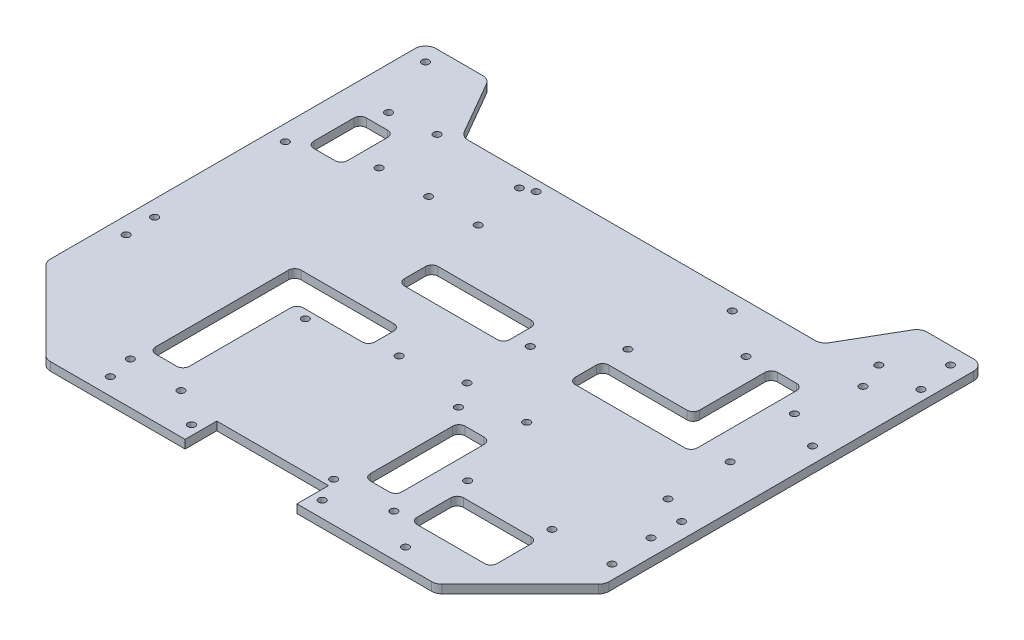
SolidWorks part; units mm, degrees
material "Acier non allié"
ref_plane "Front" through (0, 0, 0) normal (0, 0, 1) x (1, 0, 0)
ref_plane "Top" through (0, 0, 0) normal (0, 1, 0) x (1, 0, 0)
ref_plane "Right" through (0, 0, 0) normal (1, 0, 0) x (0, 0, -1)
sketch "Main scetch" plane through (0, 0, 0) normal (0, 1, 0) x (1, 0, 0)
  line L1 (0, 0) -> (132.5, 0) construction
  line L2 (0, 0) -> (0, 220) construction
  line L3 (0, 220) -> (132.5, 220) construction
  line L4 (132.5, 0) -> (132.5, 220) construction
  line L13 (-92.5, 0) -> (92.5, 0)
  line L14 (92.5, 0) -> (132.5, 40)
  line L15 (132.5, 40) -> (132.5, 220)
  line L16 (132.5, 220) -> (102.5, 220)
  line L17 (102.5, 220) -> (85.1795, 190)
  line L18 (85.1795, 190) -> (-85.1795, 190)
  line L19 (-102.5, 220) -> (-85.1795, 190)
  line L20 (-132.5, 220) -> (-102.5, 220)
  line L21 (-132.5, 40) -> (-132.5, 220)
  line L22 (-92.5, 0) -> (-132.5, 40)
  point P11 (0, 190)
  dimension "132.5" = 132.5
  dimension "D2" = 220
  dimension "D1" = 40
  dimension "D3" = 40
  dimension "D4" = 30
  dimension "D5" = 60
  dimension "D6" = 30
extrude "Main extrusion" add sketch "Main scetch" along normal blind 4
fillet "Congé1" radius 5 10 edges at (-132.5, 2, -40) (-92.5, 2, 0) (92.5, 2, 0) (132.5, 2, -40) (132.5, 2, -220) (102.5, 2, -220) (85.1795, 2, -190) (-85.1795, 2, -190) (-102.5, 2, -220) (-132.5, 2, -220)
sketch "Esquisse1" plane through (0, 4, 0) normal (0, 1, 0) x (1, 0, 0)
  line L0 (0, 0) -> (0, 218.5516) construction
  line L1 (132.5, 42.0711) -> (132.5, 215) construction
  line L2 (127.5, 220) -> (105.3868, 220) construction
  line L3 (-90.4289, 0) -> (90.4289, 0) construction
  circle A0 centre (70, 8) radius 1
  circle A1 centre (124.5, 70) radius 1
  circle A2 centre (124.5, 212) radius 1
  circle A3 centre (-124.5, 212) radius 1
  circle A4 centre (-124.5, 70) radius 1
  circle A5 centre (-70, 8) radius 1
  dimension "D1" = 2
  dimension "D2" = 2
  dimension "D3" = 2
  dimension "D4" = 8
  dimension "D5" = 8
  dimension "D6" = 8
  dimension "D7" = 8
  dimension "D8" = 70
  dimension "D9" = 70
extrude "Enlèv. mat.-Extru.1" cut sketch "Esquisse1" against normal through all
hole_wizard "Dégagement M31" positions "Esquisse2" profile "Esquisse3" hole size "M3" standard "ISO" end condition through all
sketch "Esquisse2" plane through (0, 4, 0) normal (0, 1, 0) x (1, 0, 0)
  point P0 (-124.5, 212)
  point P3 (-124.5, 70)
  point P6 (-70, 8)
  point P9 (70, 8)
  point P12 (124.5, 70)
  point P15 (124.5, 212)
sketch "Esquisse3" plane through (-124.5, 4, -212) normal (1, 0, 0) x (0, 0, 1)
  line L0 (0, 0) -> (0, 4)
  line L1 (0, 4) -> (1.7, 4)
  line L2 (1.7, 4) -> (1.7, 0)
  line L5 (1.7, 0) -> (0, 0)
  line L11 (0, -6.35) -> (0, 107.95) construction
  dimension "Diamètre du perçage jusqu'au prochain" = 3.4
  dimension "Profondeur du perçage jusqu'au prochain" = 4
sketch "Esquisse4" plane through (0, 4, 0) normal (0, 1, 0) x (1, 0, 0)
  line L0 (-132.5, 215) -> (-132.5, 42.0711) construction
  line L1 (-125, 146) -> (-125, 84) construction
  line L2 (82.2927, 190) -> (-82.2927, 190) construction
  line L3 (132.5, 42.0711) -> (132.5, 215) construction
  line L4 (-90.4289, 0) -> (90.4289, 0) construction
  line L5 (127.5, 220) -> (105.3868, 220) construction
  line L8 (-105.3868, 220) -> (-127.5, 220) construction
  line L9 (-31, 7.5) -> (31, 7.5) construction
  line L10 (125, 146) -> (125, 84) construction
  line L11 (-26.5, 0) -> (26.5, 0)
  line L12 (-26.5, 0) -> (-26.5, 15)
  line L13 (-26.5, 15) -> (26.5, 15)
  line L14 (26.5, 0) -> (26.5, 15)
  line L15 (50.5, 182.5) -> (112.5, 182.5) construction
  line L16 (-112.5, 182.5) -> (-50.5, 182.5) construction
  circle A1 centre (-68.5, 185) radius 1 construction
  circle A5 centre (72.5, 167) radius 1
  circle A6 centre (41.5, 142) radius 1
  circle A7 centre (107.5, 155) radius 1
  circle A8 centre (127.5, 195) radius 1
  circle A9 centre (112, 120) radius 1
  circle A10 centre (112.5, 90) radius 1
  circle A11 centre (17.2, 120) radius 1
  circle A12 centre (17.2, 90) radius 1
  circle A13 centre (47.5, 88) radius 1
  circle A14 centre (57.5, 50) radius 1
  circle A15 centre (97.5, 50) radius 1
  circle A16 centre (52.5, 20) radius 1
  circle A17 centre (-10, 85) radius 1
  circle A18 centre (-72.5, 20) radius 1
  circle A19 centre (107.5, 195) radius 1
  circle A23 centre (-47.5, 78) radius 1
  circle A24 centre (25.14, 78) radius 1
  circle A25 centre (-47.5, 19.07) radius 1
  circle A26 centre (25.1096, 18.82) radius 1
  circle A31 centre (-125, 146) radius 1
  circle A32 centre (-125, 84) radius 1
  circle A33 centre (-31, 7.5) radius 1
  circle A34 centre (31, 7.5) radius 1
  circle A35 centre (125, 146) radius 1
  circle A36 centre (125, 84) radius 1
  circle A37 centre (50.5, 182.5) radius 1
  circle A38 centre (112.5, 182.5) radius 1
  circle A39 centre (-112.5, 182.5) radius 1
  circle A40 centre (-50.5, 182.5) radius 1
  circle A41 centre (-45, 185) radius 1
  circle A42 centre (-45, 157.5) radius 1
  circle A43 centre (-68.5, 157.5) radius 1
  circle A44 centre (-92, 157.5) radius 1
  circle A45 centre (-92, 185) radius 1
  circle A46 centre (126, 50) radius 1.5
  point P63 (-125, 115)
  point P69 (0, 7.5)
  point P74 (0, 15)
  point P79 (125, 115)
  dimension "D4" = 2
  dimension "D13" = 2
  dimension "D16" = 2
  dimension "D19" = 2
  dimension "D24" = 2
  dimension "D25" = 2
  dimension "D28" = 2
  dimension "D30" = 2
  dimension "D32" = 2
  dimension "D36" = 2
  dimension "D37" = 2
  dimension "D40" = 2
  dimension "D48" = 2
  dimension "D49" = 2
  dimension "D50" = 2
  dimension "D52" = 2
  dimension "D11" = 2
  dimension "D12" = 2
  dimension "D65" = 2
  dimension "D66" = 2
  dimension "D72" = 2
  dimension "D73" = 2
  dimension "D77" = 2
  dimension "D78" = 2
  dimension "D85" = 2
  dimension "D86" = 2
  dimension "D89" = 2
  dimension "D90" = 2
  dimension "D94" = 2
  dimension "D95" = 2
  dimension "D58" = 2
  dimension "D59" = 2
  dimension "D62" = 2
  dimension "D63" = 2
  dimension "D69" = 2
  dimension "D99" = 3
  dimension "D14" = 205
  dimension "D15" = 23
  dimension "D20" = 25
  dimension "D21" = 65
  dimension "D22" = 5
  dimension "D23" = 25
  dimension "D26" = 20.5
  dimension "D27" = 100
  dimension "D29" = 30
  dimension "D31" = 115.3
  dimension "D33" = 115.3
  dimension "D34" = 132
  dimension "D35" = 85
  dimension "D38" = 50
  dimension "D39" = 75
  dimension "D41" = 35
  dimension "D42" = 80
  dimension "D43" = 20
  dimension "D44" = 20
  dimension "D45" = 205
  dimension "D46" = 85
  dimension "D47" = 142.5
  dimension "D51" = 25
  dimension "D53" = 25
  dimension "D54" = 5
  dimension "D55" = 64
  dimension "D7" = 59.18
  dimension "D8" = 72.64
  dimension "D9" = 58.93
  dimension "D10" = 72.61
  dimension "D67" = 85
  dimension "D68" = 78
  dimension "D17" = 25
  dimension "D18" = 31
  dimension "D76" = 62
  dimension "D74" = 7.5
  dimension "D75" = 105
  dimension "D79" = 7.5
  dimension "D80" = 132.5
  dimension "D81" = 62
  dimension "D82" = 15
  dimension "D83" = 53
  dimension "D84" = 62
  dimension "D87" = 7.5
  dimension "D88" = 105
  dimension "D91" = 62
  dimension "D92" = 7.5
  dimension "D96" = 62
  dimension "D97" = 7.5
  dimension "D98" = 20
  dimension "D93" = 20
  dimension "D56" = 87.5
  dimension "D57" = 5
  dimension "D60" = 27.5
  dimension "D61" = 23.5
  dimension "D64" = 23.5
  dimension "D70" = 27.5
  dimension "D71" = 50
  dimension "D100" = 6.5
extrude "Enlèv. mat.-Extru.2" cut sketch "Esquisse4" against normal through all
hole_wizard "Dégagement M32" positions "Esquisse5" profile "Esquisse6" hole size "M3" standard "ISO" end condition through all
sketch "Esquisse5" plane through (0, 4, 0) normal (0, 1, 0) x (1, 0, 0)
  point P9 (17.2, 120)
  point P18 (41.5, 142)
  point P21 (72.5, 167)
  point P24 (107.5, 155)
  point P27 (127.5, 195)
  point P30 (112, 120)
  point P33 (112.5, 90)
  point P36 (47.5, 88)
  point P39 (17.2, 90)
  point P42 (57.5, 50)
  point P45 (97.5, 50)
  point P48 (-10, 85)
  point P51 (-72.5, 20)
  point P54 (52.5, 20)
  point P57 (107.5, 195)
  point P86 (-47.5, 78)
  point P89 (25.14, 78)
  point P92 (-47.5, 19.07)
  point P95 (25.1096, 18.82)
  point P114 (-125, 146)
  point P117 (-125, 84)
  point P121 (-31, 7.5)
  point P124 (31, 7.5)
  point P128 (125, 146)
  point P131 (125, 84)
  point P134 (-112.5, 182.5)
  point P137 (-50.5, 182.5)
  point P140 (50.5, 182.5)
  point P143 (112.5, 182.5)
  point P146 (-92, 185)
  point P149 (-92, 157.5)
  point P152 (-68.5, 157.5)
  point P155 (-45, 157.5)
  point P158 (-45, 185)
  point P161 (126, 50)
sketch "Esquisse6" plane through (17.2, 4, -120) normal (1, 0, 0) x (0, 0, 1)
  line L0 (0, 0) -> (0, 4)
  line L1 (0, 4) -> (1.7, 4)
  line L2 (1.7, 4) -> (1.7, 0)
  line L5 (1.7, 0) -> (0, 0)
  line L11 (0, -6.35) -> (0, 107.95) construction
  dimension "Diamètre du perçage jusqu'au prochain" = 3.4
  dimension "Profondeur du perçage jusqu'au prochain" = 4
sketch "Esquisse7" plane through (0, 4, 0) normal (0, 1, 0) x (1, 0, 0)
  line L0 (-90.4289, 0) -> (-26.5, 0) construction
  line L1 (-40.5, 131) -> (9.5, 131)
  line L2 (-40.5, 131) -> (-40.5, 115)
  line L3 (-40.5, 115) -> (9.5, 115)
  line L4 (9.5, 131) -> (9.5, 115)
  line L5 (-132.5, 215) -> (-132.5, 42.0711) construction
  line L8 (40.5, 115) -> (98.5, 115)
  line L10 (132.5, 42.0711) -> (132.5, 215) construction
  line L11 (40.5, 115) -> (40.5, 131)
  line L12 (83.5, 168) -> (98.5, 168)
  line L13 (83.5, 168) -> (83.5, 131)
  line L15 (98.5, 168) -> (98.5, 115)
  line L16 (40.5, 131) -> (83.5, 131)
  line L17 (-105.3868, 220) -> (-127.5, 220) construction
  line L18 (60.5, 42) -> (98.5, 42)
  line L19 (60.5, 42) -> (60.5, 20)
  line L20 (60.5, 20) -> (98.5, 20)
  line L21 (98.5, 42) -> (98.5, 20)
  line L22 (-118.5, 175) -> (-102.5, 175)
  line L23 (-118.5, 175) -> (-118.5, 150)
  line L24 (-118.5, 150) -> (-102.5, 150)
  line L25 (-102.5, 175) -> (-102.5, 150)
  line L27 (-71.5, 28) -> (-55.5, 28)
  line L28 (-71.5, 28) -> (-71.5, 83)
  line L30 (-55.5, 28) -> (-55.5, 82)
  line L31 (31.5, 71.82) -> (46.5, 71.82)
  line L32 (31.5, 71.82) -> (31.5, 26.82)
  line L33 (31.5, 26.82) -> (46.5, 26.82)
  line L34 (46.5, 71.82) -> (46.5, 26.82)
  line L35 (-71.5, 97) -> (-21.5, 97)
  line L36 (-71.5, 97) -> (-71.5, 83)
  line L37 (-55.5, 82) -> (-21.5, 82)
  line L38 (-21.5, 97) -> (-21.5, 82)
  circle A0 centre (-72.5, 20) radius 1.7 construction
  circle A1 centre (-47.5, 78) radius 1.7 construction
  circle A2 centre (25.1096, 18.82) radius 1.7 construction
  circle A3 centre (52.5, 20) radius 1.7 construction
  dimension "D19" = 8
  dimension "D20" = 8
  dimension "D24" = 15
  dimension "D1" = 50
  dimension "D2" = 16
  dimension "D3" = 131
  dimension "D4" = 92
  dimension "D5" = 16
  dimension "D6" = 53
  dimension "D7" = 43
  dimension "D8" = 115
  dimension "D9" = 72
  dimension "D10" = 38
  dimension "D11" = 34
  dimension "D12" = 15
  dimension "D13" = 22
  dimension "D14" = 20
  dimension "D15" = 30
  dimension "D16" = 70
  dimension "D17" = 16
  dimension "D18" = 25
  dimension "D21" = 16
  dimension "D22" = 55
  dimension "D23" = 8
  dimension "6" = 6
  dimension "D25" = 45
  dimension "D26" = 50
  dimension "D27" = 54
  dimension "D28" = 15
extrude "Enlèv. mat.-Extru.3" cut sketch "Esquisse7" against normal up to surface (4 mm away) up to face at (17.2, 0, -118.3)
fillet "Congé2" radius 3 28 edges at (60.5, 2, -42) (60.5, 2, -20) (98.5, 2, -20) (98.5, 2, -42) (98.5, 2, -168) (98.5, 2, -115) (83.5, 2, -168) (40.5, 2, -131) (83.5, 2, -131) (40.5, 2, -115) (-40.5, 2, -115) (9.5, 2, -115) (9.5, 2, -131) (-40.5, 2, -131) (-118.5, 2, -150) (-102.5, 2, -150) (-102.5, 2, -175) (-118.5, 2, -175) (-55.5, 2, -28) (-71.5, 2, -28) (46.5, 2, -26.82) (31.5, 2, -26.82) (46.5, 2, -71.82) (31.5, 2, -71.82) (-21.5, 2, -82) (-21.5, 2, -97) (-55.5, 2, -82) (-71.5, 2, -97)
equation "\"WIDTH\"= 300mm'Total width of the robot"
equation "\"LENGTH\"= 220mm'Total length of the robot"
equation "\"D2@Main scetch\" = \"LENGTH\""
equation "\"CUT_DEPTH\"= 45mm'Depth of the cut on the edges of the plate"
equation "\"Plate_th\"= 3mm'Thickness of the plate"
equation "\"D1\"= \"Plate_th\""
equation "\"D47@Esquisse4\"=(80+205)/2"
